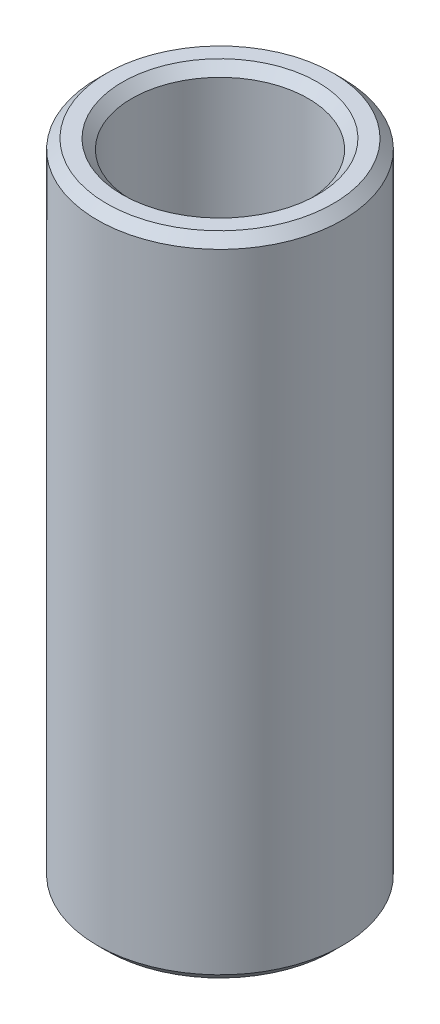
SolidWorks part; units mm, degrees
ref_plane "Front Plane" through (0, 0, 0) normal (0, 0, 1) x (1, 0, 0)
ref_plane "Top Plane" through (0, 0, 0) normal (0, 1, 0) x (1, 0, 0)
ref_plane "Right Plane" through (0, 0, 0) normal (1, 0, 0) x (0, 0, -1)
sketch "Sketch1" plane through (0, 0, 0) normal (0, 1, 0) x (1, 0, 0)
  circle A0 centre (0, 0) radius 45
  dimension "SLEEVE_OD" = 90
extrude "Boss-Extrude1" add sketch "Sketch1" along normal blind 237.479
sketch "Sketch2" plane through (0, 0, 0) normal (0, 1, 0) x (1, 0, 0)
  circle A0 centre (0, 0) radius 32.3507
  dimension "BORE_D" = 64.7014
extrude "Cut-Extrude1" cut sketch "Sketch2" along normal through all
chamfer "Chamfer1" distance 3.4642 angle 45 4 edges at (0, 237.479, 32.3507) (0, 0, 32.3507) (0, 0, 45) (0, 237.479, 45)
